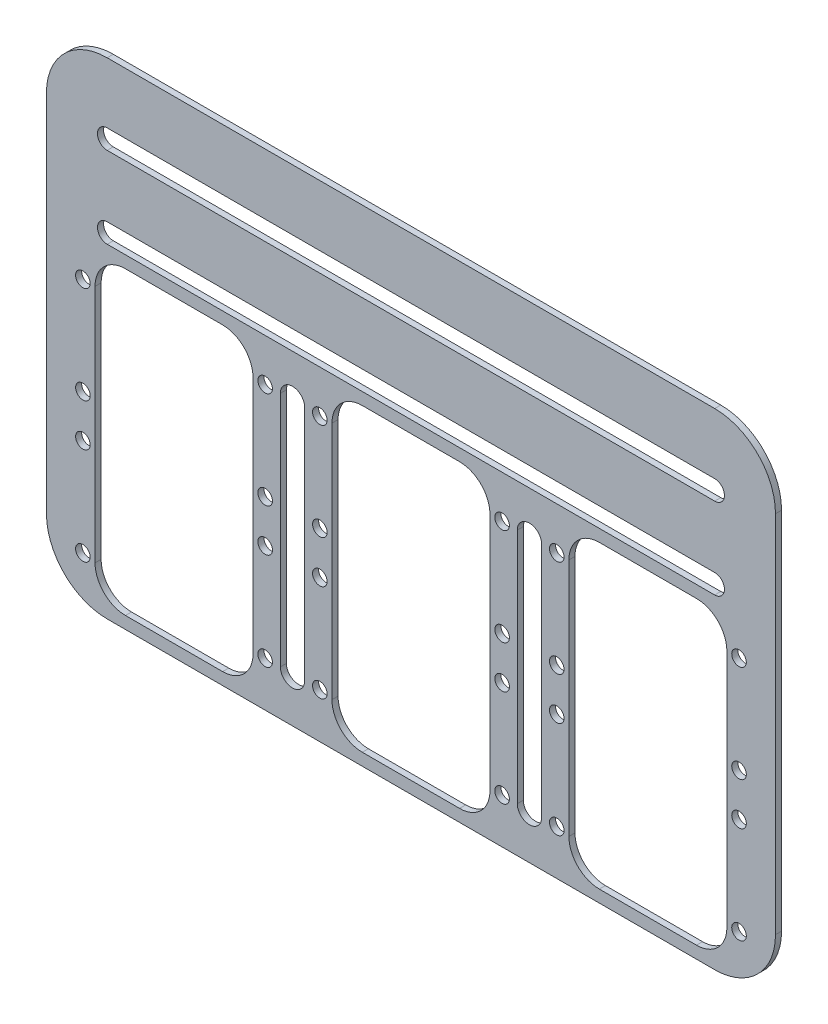
SolidWorks part; units mm, degrees
material "PET"
ref_plane "Front Plane" through (0, 0, 0) normal (0, 0, 1) x (1, 0, 0)
ref_plane "Top Plane" through (0, 0, 0) normal (0, 1, 0) x (1, 0, 0)
ref_plane "Right Plane" through (0, 0, 0) normal (1, 0, 0) x (0, 0, -1)
sketch "Sketch1" plane through (0, 0, 0) normal (0, 0, 1) x (1, 0, 0)
  line L1 (60, -40) -> (-60, -40)
  line L2 (60, -40) -> (60, 40)
  line L3 (60, 40) -> (-60, 40)
  line L4 (-60, -40) -> (-60, 40)
  line L5 (60, -40) -> (-60, 40) construction
  line L6 (60, 40) -> (-60, -40) construction
  point P0 (0, 0)
  dimension "D1" = 120
  dimension "D2" = 80
extrude "plate" add sketch "Sketch1" along normal blind 1
sketch "Sketch2" plane through (0, 0, 1) normal (0, 0, 1) x (1, 0, 0)
  line L0 (50, 28.4) -> (-50, 28.4) construction
  line L1 (50, 26.8) -> (-50, 26.8)
  line L2 (50, 30) -> (-50, 30)
  line L3 (60, 40) -> (-60, 40) construction
  line L4 (-60, 40) -> (-60, -40) construction
  arc A0 (50, 26.8) -> (50, 30) centre (50, 28.4) ccw
  arc A1 (-50, 30) -> (-50, 26.8) centre (-50, 28.4) ccw
  point P2 (0, 28.4)
  point P13 (0, 0)
  dimension "D1" = 1.6
  dimension "D2" = 10
  dimension "D3" = 10
extrude "slot_cut" cut sketch "Sketch2" against normal through all
pattern_linear "second_slot" count 2 spacing 13.38 along (0, -1, 0) of "slot_cut"
sketch "motor_outline" plane through (0, 0, 1) normal (0, 0, 1) x (1, 0, 0)
  line L0 (18.75, -11.58) -> (18.75, 8.42)
  line L1 (-20.25, -11.58) -> (-57.75, -11.58)
  line L2 (-20.25, -11.58) -> (-20.25, 8.42)
  line L3 (-20.25, 8.42) -> (-57.75, 8.42)
  line L4 (-57.75, -11.58) -> (-57.75, 8.42)
  line L5 (-20.25, -11.58) -> (-57.75, 8.42) construction
  line L6 (-20.25, 8.42) -> (-57.75, -11.58) construction
  line L7 (18.75, -11.58) -> (-18.75, -11.58)
  line L8 (-18.75, -11.58) -> (-18.75, 8.42)
  line L9 (18.75, 8.42) -> (-18.75, 8.42)
  line L10 (57.75, -11.58) -> (57.75, 8.42)
  line L11 (57.75, -11.58) -> (20.25, -11.58)
  line L12 (20.25, -11.58) -> (20.25, 8.42)
  line L13 (57.75, 8.42) -> (20.25, 8.42)
  line L14 (-18.75, 8.42) -> (18.75, -11.58) construction
  line L15 (18.75, 8.42) -> (-18.75, -11.58) construction
  line L16 (-50, 13.42) -> (50, 13.42) construction
  line L17 (-39, -1.58) -> (-39, 8.42) construction
  line L18 (-39, -1.58) -> (-57.75, -1.58) construction
  line L19 (-52, 6.42) -> (-52, -33)
  line L24 (-47, -38) -> (-31, -38)
  line L25 (-26, -33) -> (-26, 6.42)
  line L26 (-31, 11.42) -> (-47, 11.42)
  line L27 (-60, -40) -> (60, -40) construction
  circle A0 centre (-54, 6.42) radius 1.2
  circle A1 centre (-54, -9.58) radius 1.2
  circle A2 centre (-24, -9.58) radius 1.2
  circle A3 centre (-24, 6.42) radius 1.2
  arc A4 (-52, -33) -> (-47, -38) centre (-47, -33) ccw
  arc A5 (-31, -38) -> (-26, -33) centre (-31, -33) ccw
  arc A6 (-26, 6.42) -> (-31, 11.42) centre (-31, 6.42) ccw
  arc A7 (-52, 6.42) -> (-47, 11.42) centre (-47, 6.42) cw
  point P0 (-39, -1.58)
  point P6 (0, -1.58)
  point P32 (0, 0)
  point P33 (-50, 8.42)
  point P34 (-48.1505, 7.62)
  point P35 (0, 0)
  point P36 (-27.9628, 10.7759)
  dimension "D6" = 2.4
  dimension "D11" = 5
  dimension "D2" = 20
  dimension "D4" = 5
  dimension "D5" = 39
  dimension "D7" = 16
  dimension "D1" = 30
  dimension "D8" = 2
  dimension "D9" = 2
  dimension "D10" = 2
  dimension "D3" = 3
extrude "motor_mount" cut sketch "motor_outline" against normal through all contours A0 | A3 | A2 | A1
pattern_linear "motors" count 3 spacing 39 along (1, 0, 0) count 2 spacing 23 along (0, -1, 0) of "motor_mount"
extrude "motor_cutout" cut sketch "motor_outline<5>" against normal through all contours L24 A5 L25 L1 L19 A4 | A7 L19 L1 L25 A6 L3 | A7 L3 A6 L26 region at (-39, -24.5981, 1) region at (-39, -1.59, 1) region at (-39, 9.8433, 1)
sketch "motor_outline<5>" plane through (0, 0, 1) normal (0, 0, 1) x (1, 0, 0) same geometry as "motor_outline"
pattern_linear "cutout_pattern" count 3 spacing 39 along (1, 0, 0) of "motor_cutout"
fillet "Fillet1" radius 10 4 edges at (-60, -40, 0.5) (60, -40, 0.5) (60, 40, 0.5) (-60, 40, 0.5)
sketch "Sketch4" plane through (0, 0, 1) normal (0, 0, 1) x (1, 0, 0)
  line L0 (-24, 6.42) -> (-15, 6.42) construction
  line L1 (-24, -32.58) -> (-15, -32.58) construction
  line L2 (-19.5, 6.42) -> (-19.5, -32.58) construction
  line L3 (-17.5, 6.42) -> (-17.5, -32.58)
  line L4 (-21.5, 6.42) -> (-21.5, -32.58)
  circle A0 centre (-15, 6.42) radius 1.2 construction
  circle A1 centre (-24, 6.42) radius 1.2 construction
  circle A2 centre (-15, 6.42) radius 1.2 construction
  circle A3 centre (-24, 6.42) radius 1.2 construction
  arc A4 (-17.5, 6.42) -> (-21.5, 6.42) centre (-19.5, 6.42) ccw
  arc A5 (-21.5, -32.58) -> (-17.5, -32.58) centre (-19.5, -32.58) ccw
  point P6 (-19.5, 6.42)
  point P10 (-19.5, -32.58)
  point P11 (-19.5, -13.08)
  dimension "D1" = 2
extrude "Cut-Extrude5" cut sketch "Sketch4" against normal through all
pattern_linear "LPattern6" count 2 spacing 39 along (1, 0, 0) of "Cut-Extrude5"
equation "\"d\"= 10'distance from slot to the side"
equation "\"D3@Sketch2\"=\"d\""
equation "\"a\"= 120'palm size"
equation "\"D1@Sketch1\"=\"a\""
equation "\"spacing\"= 39'for linear patterns"
equation "\"D5@motor_outline\"=\"spacing\""
equation "\"D3@motors\"=\"spacing\""
equation "\"D3@cutout_pattern\"=\"spacing\""
equation "\"D3@LPattern6\"=\"spacing\""
